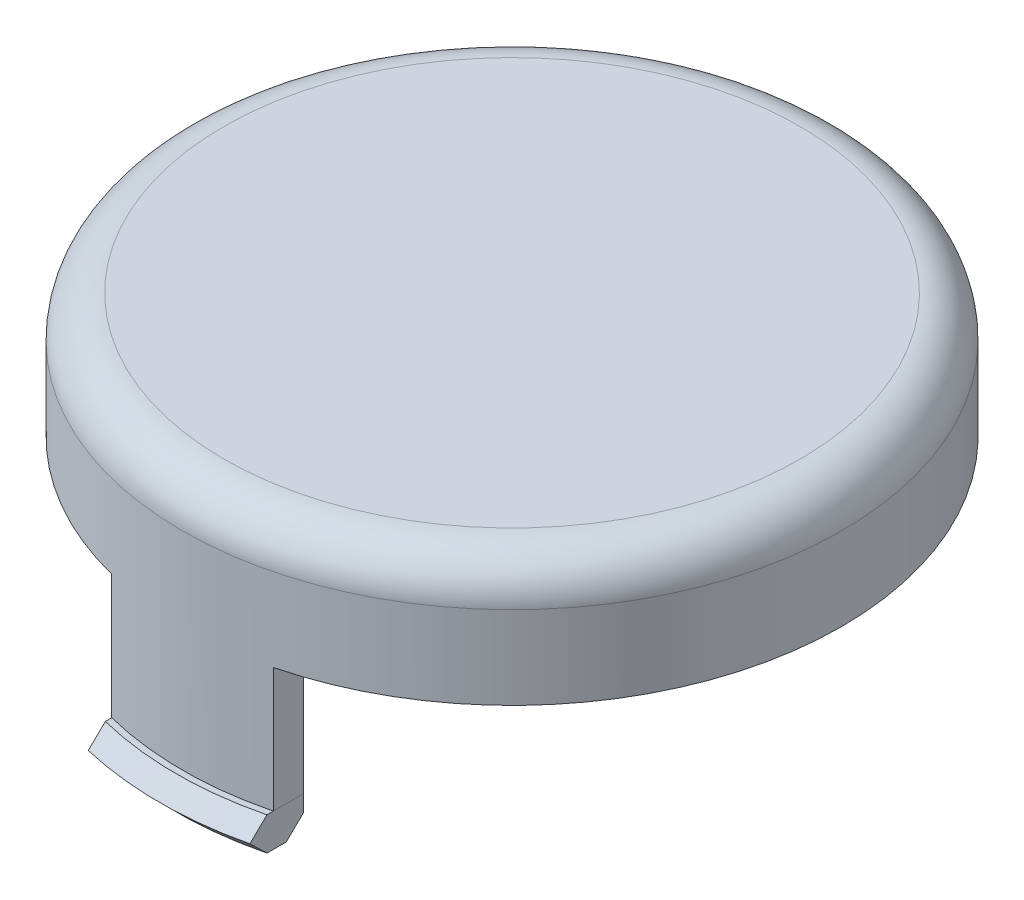
SolidWorks part; units mm, degrees
ref_plane "前视基准面" through (0, 0, 0) normal (0, 0, 1) x (1, 0, 0)
ref_plane "上视基准面" through (0, 0, 0) normal (0, 1, 0) x (1, 0, 0)
ref_plane "右视基准面" through (0, 0, 0) normal (1, 0, 0) x (0, 0, -1)
sketch "草图2" plane through (0, 0, 0) normal (0, 1, 0) x (1, 0, 0)
  circle A0 centre (0, 0) radius 7.95
  dimension "D1" = 15.9
extrude "凸台-拉伸1" add sketch "草图2" along normal blind 4
sketch "草图4" plane through (0, 0, 0) normal (0, -1, 0) x (1, 0, 0)
  circle A2 centre (0, 0) radius 8.5
  dimension "D1" = 17
extrude "凸台-拉伸2" add sketch "草图4" along normal blind 0.8 separate body
sketch "草图3" plane through (0, -0.8, 0) normal (0, -1, 0) x (1, 0, 0)
  circle A0 centre (0, 0) radius 7.25
  dimension "D1" = 14.5
extrude "切除-拉伸2" cut sketch "草图3" against normal blind 3.8
chamfer "倒角2" distance 0.4 angle 45 3 edges at (0, -0.8, -7.25) (0, -0.8, -8.5) (0, 0, -8.5)
sketch "草图5" plane through (0, 0, 0) normal (0, 0, 1) x (1, 0, 0)
  line L0 (-7.95, 4) -> (-7.95, 0) construction
  line L1 (-1.95, 3) -> (-7.95, 3)
  line L2 (-1.95, 3) -> (-1.95, -5)
  line L3 (-1.95, -5) -> (-7.95, -5)
  line L4 (-7.95, 3) -> (-7.95, -5)
  line L6 (1.95, 3) -> (7.95, 3)
  line L7 (1.95, 3) -> (1.95, -5)
  line L8 (1.95, -5) -> (7.95, -5)
  line L9 (7.95, 3) -> (7.95, -5)
  line L11 (7.95, 0) -> (7.95, 4) construction
  line L12 (7.95, 4) -> (-7.95, 4) construction
  point P10 (0, 0)
  point P13 (0, 0)
  point P14 (0, 0)
  point P15 (0, 0)
  dimension "D1" = 6
  dimension "D2" = 6
  dimension "D3" = 8
  dimension "D4" = 1
extrude "切除-拉伸3" cut sketch "草图5" against normal through all and the other way through all
sketch "草图6" plane through (0, 4, 0) normal (0, 1, 0) x (1, 0, 0)
  circle A1 centre (0, 0) radius 7.95
  circle A2 centre (0, 0) radius 7.95
  dimension "D1" = 0
extrude "凸台-拉伸3" add sketch "草图6" along normal blind 2
fillet "圆角1" radius 1 1 edges at (0, 6, 7.95)
sketch "草图7" plane through (0, 3, 0) normal (0, -1, 0) x (1, 0, 0)
  circle A0 centre (0, 0) radius 6.5
  dimension "D1" = 13
extrude "切除-拉伸4" cut sketch "草图7" against normal blind 1
sketch "草图9" plane through (0, 0, 0) normal (0, 0, 1) x (1, 0, 0)
  line L1 (-9.148, 0.757) -> (-7.1332, 0.757)
  line L2 (-9.148, 0.757) -> (-9.148, -1.5563)
  line L3 (-9.148, -1.5563) -> (-7.1332, -1.5563)
  line L4 (-7.1332, 0.757) -> (-7.1332, -1.5563)
  line L5 (6.871, 0.757) -> (8.8138, 0.757)
  line L6 (6.871, 0.757) -> (6.871, -2.1388)
  line L7 (6.871, -2.1388) -> (8.8138, -2.1388)
  line L8 (8.8138, 0.757) -> (8.8138, -2.1388)
  spline S0 degree 3 poles (9.5394, 0.8749) (9.4567, 0.8749) (9.365, 0.8242) (9.2205, 0.6789) (9.1722, 0.6199) (9.0765, 0.4809) (9.0287, 0.3998) (8.9382, 0.2204) (8.8957, 0.1222) (8.8178, -0.0918) (8.7822, -0.2093) (8.7239, -0.4533) (8.7008, -0.5805) (8.6689, -0.8458) (8.6605, -0.984) (8.6601, -1.2559) (8.668, -1.3929) (8.6993, -1.6604) (8.7222, -1.7887) (8.8096, -2.1579) (8.8915, -2.3773) (9.0277, -2.6483) (9.0748, -2.7282) (9.1708, -2.8683) (9.2201, -2.9286) (9.3158, -3.0251) (9.3627, -3.0619) (9.4538, -3.112) (9.498, -3.1251) (9.5394, -3.1251) knots 0 0 0 0 0.125 0.125 0.1875 0.1875 0.25 0.25 0.3125 0.3125 0.375 0.375 0.4375 0.4375 0.5 0.5 0.5625 0.5625 0.625 0.625 0.75 0.75 0.8125 0.8125 0.875 0.875 0.9375 0.9375 1 1 1 1 construction
  spline S1 degree 3 poles (9.5394, -3.1251) (9.4567, -3.1251) (9.365, -3.0744) (9.2205, -2.9291) (9.1722, -2.8701) (9.0765, -2.731) (9.0287, -2.65) (8.9382, -2.4706) (8.8957, -2.3724) (8.8178, -2.1584) (8.7822, -2.0409) (8.7239, -1.7969) (8.7008, -1.6697) (8.6689, -1.4044) (8.6605, -1.2662) (8.6601, -0.9943) (8.668, -0.8573) (8.6993, -0.5898) (8.7222, -0.4615) (8.8096, -0.0923) (8.8915, 0.1271) (9.0277, 0.3981) (9.0748, 0.478) (9.1708, 0.6181) (9.2201, 0.6784) (9.3158, 0.7749) (9.3627, 0.8117) (9.4538, 0.8618) (9.498, 0.8749) (9.5394, 0.8749) knots 0 0 0 0 0.125 0.125 0.1875 0.1875 0.25 0.25 0.3125 0.3125 0.375 0.375 0.4375 0.4375 0.5 0.5 0.5625 0.5625 0.625 0.625 0.75 0.75 0.8125 0.8125 0.875 0.875 0.9375 0.9375 1 1 1 1 construction
extrude "切除-拉伸8" cut sketch "草图9" against normal through all and the other way through all
